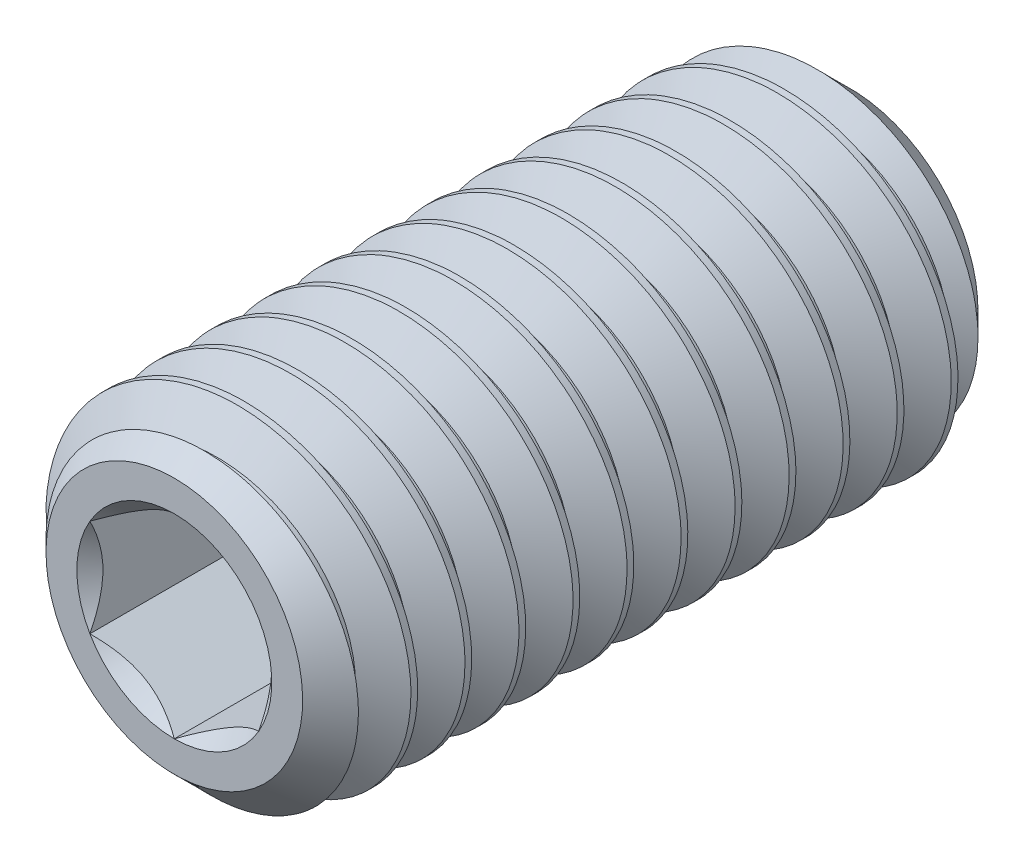
SolidWorks part; units mm, degrees
ref_plane "Front Plane" through (0, 0, 0) normal (0, 0, 1) x (1, 0, 0)
ref_plane "Top Plane" through (0, 0, 0) normal (0, 1, 0) x (1, 0, 0)
ref_plane "Right Plane" through (0, 0, 0) normal (1, 0, 0) x (0, 0, -1)
sketch "Sketch1" plane through (0, 0, 0) normal (1, 0, 0) x (0, 0, -1)
  line L0 (-5, 0) -> (5, 0) construction
  line L1 (-5, -2.5) -> (-5, 2.5) construction
  line L2 (-5, -1.25) -> (-5, 1.25) construction
  line L3 (-5, 2.5) -> (5, 2.5) construction
  line L4 (5, 2.5) -> (5, 0) construction
  line L5 (-5.75, 2.5866) -> (-4.95, 2.5866)
  line L6 (-4.95, 2.5866) -> (-5.35, 1.8938)
  line L7 (-5.35, 1.8938) -> (-5.75, 2.5866)
  line L8 (-5.35, 1.8938) -> (-5.35, 1.9804)
  line L9 (-5.35, 2.5866) -> (-5.35, 2.5)
  line L10 (-5.7, 2.5) -> (-5, 2.5)
  line L11 (-5.725, 2.5433) -> (-4.975, 2.5433)
  line L12 (-5.4, 1.9804) -> (-5.3, 1.9804)
  point P3 (-3.8, -2.5)
  point P4 (0, 0)
  point P8 (-5, 0)
  point P11 (-5, 0)
  point P21 (-5.35, 2.5)
  point P24 (-5.35, 2.5433)
  point P27 (-5.35, 1.9804)
  dimension "Length" = 10
  dimension "Thread Size" = 5
  dimension "Drive Size" = 2.5
  dimension "Thread Pitch" = 0.8
  dimension "D1" = 0.1
  dimension "D2" = 1.2
sketch "Sketch2" plane through (0, 0, 0) normal (1, 0, 0) x (0, 0, -1)
  line L1 (-5, 0) -> (5, 0)
  line L2 (-5, 0) -> (-5, 2.5)
  line L3 (-5, 2.5) -> (5, 2.5)
  line L4 (5, 0) -> (5, 2.5)
revolve "Revolve1" add sketch "Sketch2" angle 360 about L1
chamfer "Chamfer1" distance 0.6 angle 45 2 edges at (0, -2.5, -5) (0, -2.5, 5)
sketch "Sketch3" plane through (0, 0, 5) normal (0, 0, 1) x (1, 0, 0)
  line L0 (0, -1.25) -> (0, 1.25) construction
  line L1 (0, 1.4434) -> (-1.25, 0.7217)
  line L2 (-1.25, 0.7217) -> (-1.25, -0.7217)
  line L3 (-1.25, -0.7217) -> (0, -1.4434)
  line L4 (0, -1.4434) -> (1.25, -0.7217)
  line L5 (1.25, -0.7217) -> (1.25, 0.7217)
  line L6 (1.25, 0.7217) -> (0, 1.4434)
  line L7 (0, -2.5) -> (0, 2.5) construction
  circle A0 centre (0, 0) radius 1.25 construction
extrude "Cut-Extrude1" cut sketch "Sketch3" against normal blind 4.38
sketch "Sketch4" plane through (0, 0, 5) normal (0, 0, 1) x (1, 0, 0)
  line L0 (0, -2.5) -> (0, 2.5) construction
  circle A0 centre (0, 0) radius 1.4434
extrude "Cut-Extrude2" cut sketch "Sketch4" against normal blind 4.38 draft 45
sketch "Sketch5" plane through (0, 0, 5) normal (0, 0, 1) x (1, 0, 0)
  line L0 (0, -2.5) -> (0, 2.5) construction
  circle A0 centre (0, 0) radius 2.5
curve "Helix/Spiral1" pitch 0.8 height 10.8 turns 13.5
sketch "Sketch6" plane through (0, 0, 0) normal (1, 0, 0) x (0, 0, -1)
  line L0 (-5.725, 2.5433) -> (-4.975, 2.5433)
  line L1 (-4.975, 2.5433) -> (-5.3, 1.9804)
  line L2 (-5.3, 1.9804) -> (-5.4, 1.9804)
  line L3 (-5.4, 1.9804) -> (-5.725, 2.5433)
sweep "Cut-Sweep1" cut profiles "Sketch6" path "Helix/Spiral1"
equation "\"D1@Sketch1\"=\"Thread Pitch@Sketch1\"/8"
equation "\"D1@Chamfer1\"=\"Thread Pitch@Sketch1\"*.75"
equation "\"D1@Cut-Extrude1\"=\"Length@Sketch1\"*.438"
equation "\"D1@Cut-Extrude2\"=\"D1@Cut-Extrude1\""
equation "\"D4@Helix/Spiral1\"=\"Thread Pitch@Sketch1\""
equation "\"D3@Helix/Spiral1\"=\"Thread Pitch@Sketch1\"+\"Length@Sketch1\""
equation "\"D2@Sketch1\"=\"Thread Pitch@Sketch1\"*1.5"
